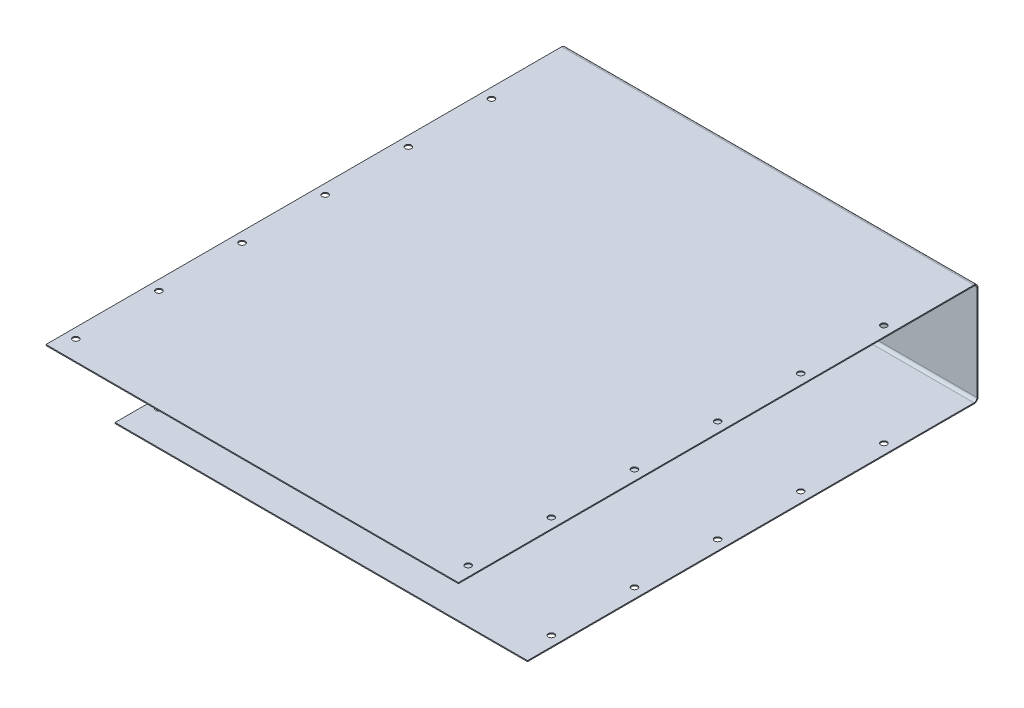
SolidWorks part; units mm, degrees
note: The reader was unsure of these and kept them because the rebuilt part matched: flange length of "Edge-Flange1", "Edge-Flange2".
material "1.0037 (S235JR)"
ref_plane "Front Plane" through (0, 0, 0) normal (0, 0, 1) x (1, 0, 0)
ref_plane "Top Plane" through (0, 0, 0) normal (0, 1, 0) x (1, 0, 0)
ref_plane "Right Plane" through (0, 0, 0) normal (1, 0, 0) x (0, 0, -1)
sketch "Sketch1" plane through (0, 0, 0) normal (0, 1, 0) x (1, 0, 0)
  line L1 (-206, -257.5) -> (206, -257.5)
  line L2 (-206, -257.5) -> (-206, 257.5)
  line L3 (-206, 257.5) -> (206, 257.5)
  line L4 (206, -257.5) -> (206, 257.5)
  line L5 (-206, -257.5) -> (206, 257.5) construction
  line L6 (-206, 257.5) -> (206, -257.5) construction
  point P0 (0, 0)
  dimension "D1" = 515
  dimension "D2" = 412
base flange "Base-Flange1" sketch "Sketch1" thickness 1 reverse thickness direction no parameters "D1"=3
edge flange "Edge-Flange1" sketch "Sketch8" flange angle 90 flange length 99 flange position bend outside bend radius 3 thickness 1 relief rectangular parameters "D6"=10
sketch "Sketch8" plane through (0, -1, -257.5) normal (0, 0, 1) x (-1, 0, 0)
  line L2 (-206, 0) -> (-206, 98)
  line L3 (-206, 98) -> (206, 98)
  line L4 (206, 98) -> (206, 0)
  line L5 (206, 0) -> (-206, 0) construction
  line L6 (206, 0) -> (-206, 0)
bend "EdgeBend1" bend radius 3 bend angle 90 parameters "D5"=1
edge flange "Edge-Flange2" sketch "Sketch11" flange angle 90 flange length 450 flange position bend outside bend radius 3 thickness 1 relief rectangular parameters "D6"=10
sketch "Sketch11" plane through (0, -99, -260.5) normal (0, -1, 0) x (1, 0, 0)
  line L0 (-206, 0) -> (206, 0) construction
  line L1 (-206, 0) -> (206, 0)
  line L2 (-206, 0) -> (-206, 449)
  line L3 (-206, 449) -> (206, 449)
  line L4 (206, 449) -> (206, 0)
bend "EdgeBend2" bend radius 3 bend angle 90 parameters "D5"=2
sketch "Sketch12" plane through (0, 0, 0) normal (0, 1, 0) x (1, 0, 0)
  line L0 (0, 0) -> (0, 121.8187) construction
  line L1 (196, 177.5) -> (196, 257.5) construction
  line L2 (206, 257.5) -> (-206, 257.5) construction
  line L3 (206, -257.5) -> (206, 257.5) construction
  line L4 (196, 94.45) -> (196, 174.45) construction
  line L5 (196, 11.4) -> (196, 91.4) construction
  line L6 (196, -71.65) -> (196, 8.35) construction
  line L7 (196, -154.7) -> (196, -74.7) construction
  line L8 (196, -237.75) -> (196, -157.75) construction
  line L9 (-196, -237.75) -> (-196, -157.75) construction
  line L10 (-196, -154.7) -> (-196, -74.7) construction
  line L11 (-196, -71.65) -> (-196, 8.35) construction
  line L12 (-196, 11.4) -> (-196, 91.4) construction
  line L13 (-196, 94.45) -> (-196, 174.45) construction
  line L14 (-196, 177.5) -> (-196, 257.5) construction
  circle A0 centre (196, 177.5) radius 3.05
  circle A1 centre (196, 94.45) radius 3.05
  circle A2 centre (196, 11.4) radius 3.05
  circle A3 centre (196, -71.65) radius 3.05
  circle A4 centre (196, -154.7) radius 3.05
  circle A5 centre (196, -237.75) radius 3.05
  circle A6 centre (-196, -237.75) radius 3.05
  circle A7 centre (-196, -154.7) radius 3.05
  circle A8 centre (-196, -71.65) radius 3.05
  circle A9 centre (-196, 11.4) radius 3.05
  circle A10 centre (-196, 94.45) radius 3.05
  circle A11 centre (-196, 177.5) radius 3.05
  dimension "D1" = 6.1
  dimension "D2" = 10
  dimension "D3" = 80
  dimension "D4" = 6
extrude "Cut-Extrude1" cut sketch "Sketch12" against normal through all both and the other way through all
sketch "Bend-Lines1" [suppressed] plane through (0, 0, 0) normal (0, 1, 0) x (1, 0, 0)
sketch "Bounding-Box1" [suppressed] plane through (0, 0, 0) normal (0, 1, 0) x (1, 0, 0)
sheet metal parameters "Sheet-Metal1" thickness 1 parameters "D1"=1
flat pattern "Flat-Pattern1" [suppressed]
sketch "Bend-Lines2" plane through (0, 0, 0) normal (0, 1, 0) x (1, 0, 0)
sketch3d "Bounding-Box2" [suppressed]
  line L0 (206, -257.5, 0) -> (206, 257.5, 0) construction
  line L1 (-206, -257.5, 0) -> (-206, 257.5, 0) construction
  line L2 (206, -257.5, 0) -> (-206, -257.5, 0) construction
  line L3 (206, 257.5, 0) -> (-206, 257.5, 0) construction
sheet metal parameters "Sheet-Metal2" thickness 1 parameters "D1"=1
flat pattern "Flat-Pattern1"
sketch "Bend-Lines2" plane through (0, 0, 0) normal (0, 1, 0) x (1, 0, 0)
  line L0 (206, 261.7412) -> (-206, 261.7412) construction
  line L1 (206, 261.7412) -> (-206, 261.7412) construction
sketch3d "Bounding-Box2" [suppressed]
  line L0 (-206, -257.5, 0) -> (-206, 357.9823, 0) construction
  line L1 (206, -257.5, 0) -> (206, 357.9823, 0) construction
  line L2 (-206, -257.5, 0) -> (206, -257.5, 0) construction
  line L3 (-206, 357.9823, 0) -> (206, 357.9823, 0) construction
bend of the flat pattern "Flatten-<EdgeBend1>1"
sheet metal parameters "Sheet-Metal3" thickness 1 parameters "D1"=1
flat pattern "Flat-Pattern1"
sketch "Bend-Lines2" plane through (0, 0, 0) normal (0, 1, 0) x (1, 0, 0)
  line L0 (206, 261.7412) -> (-206, 261.7412) construction
  line L1 (206, 261.7412) -> (-206, 261.7412) construction
  line L2 (206, 361.6527) -> (-206, 361.6527) construction
  line L3 (206, 361.6527) -> (-206, 361.6527) construction
sketch3d "Bounding-Box2" [suppressed]
  line L0 (-206, -257.5, 0) -> (-206, 810.323, 0) construction
  line L1 (206, -257.5, 0) -> (206, 810.323, 0) construction
  line L2 (-206, -257.5, 0) -> (206, -257.5, 0) construction
  line L3 (-206, 810.323, 0) -> (206, 810.323, 0) construction
bend of the flat pattern "Flatten-<EdgeBend1>1"
bend of the flat pattern "Flatten-<EdgeBend2>1"
sheet metal parameters "Sheet-Metal4" thickness 1 parameters "D1"=1
flat pattern "Flat-Pattern1"
sketch "Bend-Lines2" plane through (0, 0, 0) normal (0, 1, 0) x (1, 0, 0)
  line L0 (206, 260.1704) -> (-206, 260.1704) construction
  line L1 (206, 260.1704) -> (-206, 260.1704) construction
  line L2 (206, 360.5111) -> (-206, 360.5111) construction
  line L3 (206, 360.5111) -> (-206, 360.5111) construction
sketch3d "Bounding-Box2" [suppressed]
  line L0 (-206, -257.5, 0) -> (-206, 809.1814, 0) construction
  line L1 (206, -257.5, 0) -> (206, 809.1814, 0) construction
  line L2 (-206, -257.5, 0) -> (206, -257.5, 0) construction
  line L3 (-206, 809.1814, 0) -> (206, 809.1814, 0) construction
bend of the flat pattern "Flatten-<EdgeBend1>1"
bend of the flat pattern "Flatten-<EdgeBend2>1"
